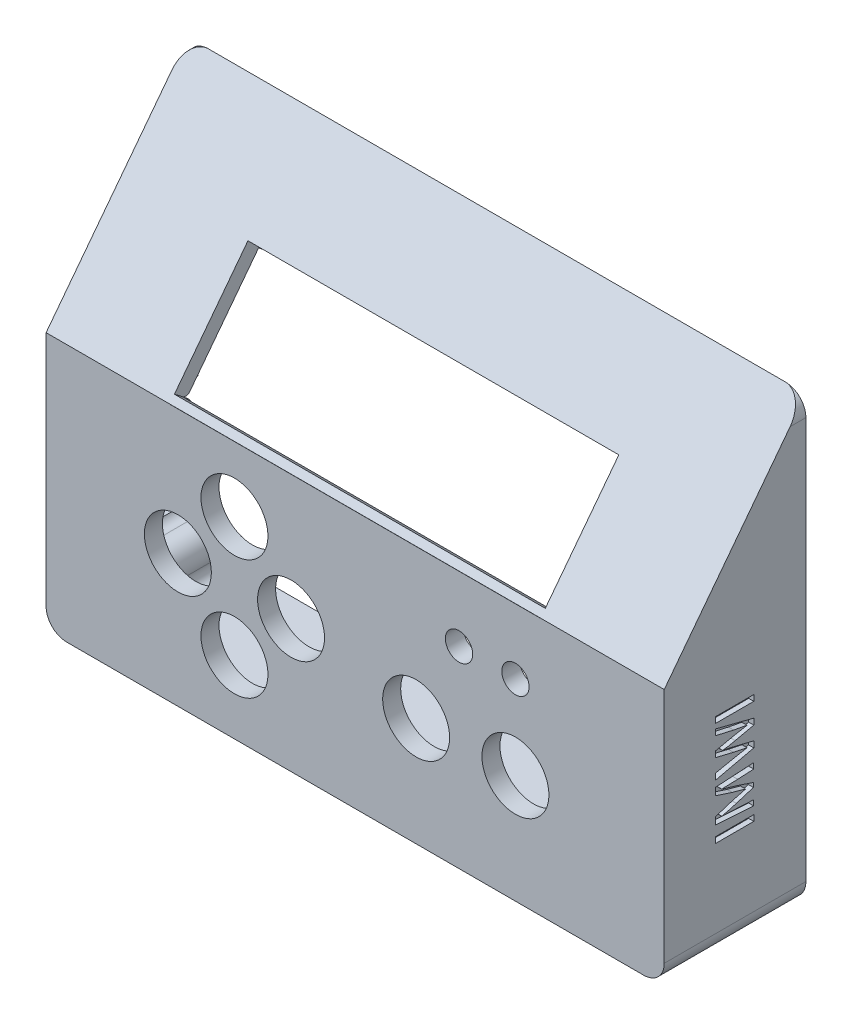
SolidWorks part; units mm, degrees
ref_plane "Front Plane" through (0, 0, 0) normal (0, 0, 1) x (1, 0, 0)
ref_plane "Top Plane" through (0, 0, 0) normal (0, 1, 0) x (1, 0, 0)
ref_plane "Right Plane" through (0, 0, 0) normal (1, 0, 0) x (0, 0, -1)
sketch "Sketch2" plane through (0, 0, 0) normal (0, 0, 1) x (1, 0, 0)
  line L0 (-36, 7) -> (36, 32) construction
  line L1 (-56, -43) -> (56, -43)
  line L2 (-60, -39) -> (-60, 39)
  line L3 (-56, 43) -> (56, 43)
  line L4 (60, -39) -> (60, 39)
  line L5 (-60, -43) -> (60, 43) construction
  line L7 (-36, 32) -> (36, 32)
  line L8 (-36, 32) -> (-36, 7)
  line L9 (-36, 7) -> (36, 7)
  line L10 (36, 32) -> (36, 7)
  line L11 (0, 43) -> (0, -43) construction
  line L12 (-23.4344, -5.6413) -> (-12.4484, -17.2736) construction
  line L13 (-12.4484, -17.2736) -> (-23.4344, -28.9058) construction
  line L14 (-23.4344, -28.9058) -> (-34.4203, -17.2736) construction
  line L15 (-34.4203, -17.2736) -> (-23.4344, -5.6413) construction
  line L16 (-23.4344, -5.6413) -> (-23.4344, -28.9058) construction
  line L17 (-12.4484, -17.2736) -> (-34.4203, -17.2736) construction
  circle A0 centre (-23.4344, -5.6413) radius 6.5
  circle A1 centre (-12.4484, -17.2736) radius 6.5
  circle A2 centre (-34.4203, -17.2736) radius 6.5
  circle A3 centre (-23.4344, -28.9058) radius 6.5
  circle A4 centre (11.8343, -21.8914) radius 6.5
  circle A5 centre (31.1116, -21.8914) radius 6.5
  circle A6 centre (20.1586, -5.6413) radius 2.65
  circle A7 centre (31.1116, -5.6413) radius 2.65
  arc A8 (-56, -43) -> (-60, -39) centre (-56, -39) cw
  arc A9 (56, -43) -> (60, -39) centre (56, -39) ccw
  arc A10 (56, 43) -> (60, 39) centre (56, 39) cw
  arc A11 (-60, 39) -> (-56, 43) centre (-56, 39) cw
  point P0 (0, 0)
  point P20 (0, 19.5)
  point P29 (0, 0)
  point P46 (60, -43)
  dimension "D3" = 72
  dimension "D6" = 11
  dimension "D7" = 4
  dimension "D1" = 86
  dimension "D2" = 120
  dimension "D4" = 25
  dimension "D5" = 16
extrude "Boss-Extrude1" add sketch "Sketch2" along normal blind 2.5
sketch "Sketch3" plane through (0, 0, 0) normal (0, 0, -1) x (-1, 0, 0)
  line L0 (60, 39) -> (60, -39) construction
  line L1 (56, -43) -> (-56, -43) construction
  line L2 (-60, -39) -> (-60, 39) construction
  line L3 (-56, 43) -> (56, 43) construction
  line L4 (60, 39) -> (60, -39)
  line L5 (56, -43) -> (-56, -43)
  line L6 (-60, -39) -> (-60, 39)
  line L7 (-56, 43) -> (56, 43)
  line L9 (-54, 41) -> (54, 41)
  line L10 (-58, 37) -> (-58, -37)
  line L11 (-54, -41) -> (54, -41)
  line L12 (58, 37) -> (58, -37)
  line L13 (-58, 41) -> (58, -41) construction
  line L14 (-58, -41) -> (58, 41) construction
  arc A0 (60, 39) -> (56, 43) centre (56, 39) ccw construction
  arc A1 (56, -43) -> (60, -39) centre (56, -39) ccw construction
  arc A2 (-60, -39) -> (-56, -43) centre (-56, -39) ccw construction
  arc A3 (-56, 43) -> (-60, 39) centre (-56, 39) ccw construction
  arc A4 (60, 39) -> (56, 43) centre (56, 39) ccw
  arc A5 (56, -43) -> (60, -39) centre (56, -39) ccw
  arc A6 (-60, -39) -> (-56, -43) centre (-56, -39) ccw
  arc A7 (-56, 43) -> (-60, 39) centre (-56, 39) ccw
  arc A8 (-58, 37) -> (-54, 41) centre (-54, 37) cw
  arc A9 (-58, -37) -> (-54, -41) centre (-54, -37) ccw
  arc A10 (58, -37) -> (54, -41) centre (54, -37) cw
  arc A11 (54, 41) -> (58, 37) centre (54, 37) cw
  point P3 (0, 0)
  dimension "D5" = 4
  dimension "D1" = 2
  dimension "D2" = 2
  dimension "D3" = 2
  dimension "D4" = 2
extrude "Boss-Extrude2" add sketch "Sketch3" along normal blind 25
sketch "Sketch5" plane through (0, 0, 0) normal (0, 0, -1) x (-1, 0, 0)
  circle A0 centre (23.4344, -28.9058) radius 6.5 construction
  circle A1 centre (34.4203, -17.2736) radius 6.5 construction
  circle A2 centre (23.4344, -5.6413) radius 6.5 construction
  circle A3 centre (12.4484, -17.2736) radius 6.5 construction
  circle A4 centre (-11.8343, -21.8914) radius 6.5 construction
  circle A5 centre (-20.1586, -5.6413) radius 2.65 construction
  circle A6 centre (-31.1116, -5.6413) radius 2.65 construction
  circle A7 centre (-31.1116, -21.8914) radius 6.5 construction
  circle A8 centre (23.4344, -28.9058) radius 6.5
  circle A9 centre (34.4203, -17.2736) radius 6.5
  circle A10 centre (23.4344, -5.6413) radius 6.5
  circle A11 centre (12.4484, -17.2736) radius 6.5
  circle A12 centre (-11.8343, -21.8914) radius 6.5
  circle A13 centre (-20.1586, -5.6413) radius 2.65
  circle A14 centre (-31.1116, -5.6413) radius 2.65
  circle A15 centre (-31.1116, -21.8914) radius 6.5
  circle A16 centre (-31.1116, -5.6413) radius 3.75
  circle A17 centre (-20.1586, -5.6413) radius 3.75
  circle A18 centre (-31.1116, -21.8914) radius 7.5
  circle A19 centre (-11.8343, -21.8914) radius 7.5
  circle A20 centre (12.4484, -17.2736) radius 7.5
  circle A21 centre (23.4344, -5.6413) radius 7.5
  circle A22 centre (34.4203, -17.2736) radius 7.5
  circle A23 centre (23.4344, -28.9058) radius 7.5
sketch "Sketch7" plane through (0, 0, 0) normal (0, 0, -1) x (-1, 0, 0)
  line L0 (0, 41) -> (0, -41) construction
  line L1 (54, 41) -> (-54, 41) construction
  line L2 (-54, -41) -> (54, -41) construction
  line L3 (-58, 0) -> (58, 0) construction
  line L4 (-58, 37) -> (-58, -37) construction
  line L5 (58, -37) -> (58, 37) construction
  line L6 (54, 41) -> (-54, 41) construction
  line L7 (58, -37) -> (58, 37)
  line L8 (54, 41) -> (-54, 41)
  line L9 (-58, -37) -> (-58, 37)
  circle A0 centre (54.5, 37.5) radius 1.7
  arc A1 (53.3, 41) -> (58, 36.3) centre (54.5, 37.5) ccw
  arc A2 (58, 37) -> (54, 41) centre (54, 37) ccw construction
  arc A3 (58, 37) -> (54, 41) centre (54, 37) ccw
  circle A4 centre (54.5, -37.5) radius 1.7
  arc A5 (53.3, -41) -> (58, -36.3) centre (54.5, -37.5) cw
  arc A6 (-53.3, -41) -> (-58, -36.3) centre (-54.5, -37.5) ccw
  circle A7 centre (-54.5, -37.5) radius 1.7
  arc A8 (-58, 37) -> (-54, 41) centre (-54, 37) cw
  arc A9 (-53.3, 41) -> (-58, 36.3) centre (-54.5, 37.5) cw
  circle A10 centre (-54.5, 37.5) radius 1.7
  arc A11 (54, -41) -> (58, -37) centre (54, -37) ccw construction
  arc A12 (-58, -37) -> (-54, -41) centre (-54, -37) ccw construction
  arc A13 (54, -41) -> (58, -37) centre (54, -37) ccw
  arc A14 (-58, -37) -> (-54, -41) centre (-54, -37) ccw
  arc M8 (-54, 41) -> (-58, 37) centre (-54, 37) ccw
  line M9 (-58, 37) -> (-58, -37)
  arc M10 (-58, -37) -> (-54, -41) centre (-54, -37) ccw
  line M11 (-54, -41) -> (54, -41)
  arc M12 (54, -41) -> (58, -37) centre (54, -37) ccw
  line M13 (58, -37) -> (58, 37)
  arc M14 (58, 37) -> (54, 41) centre (54, 37) ccw
  line M15 (54, 41) -> (-54, 41)
  dimension "D1" = 54.5
  dimension "D2" = 37.5
extrude "Boss-Extrude6" add sketch "Sketch7" along normal up to surface (25 mm away) contours A5 A4 M11 M12 M13 | A1 L7 A0 M15 M14 | A9 A10 M15 M8 M9 | A6 L9 A7 M11 M10 region at (-56.7564, -39.7564, 0) region at (-51.9557, 34.9557, 0) region at (53.65, -40.8982, 0) region at (51.9557, 34.9557, 0) up to face at (0, 0, -25)
fillet "Fillet2" radius 2 8 edges at (-53.3, -41, -12.5) (-58, -36.3, -12.5) (53.3, -41, -12.5) (58, -36.3, -12.5) (53.3, 41, -12.5) (58, 36.3, -12.5) (-53.3, 41, -12.5) (-58, 36.3, -12.5)
sketch "Sketch8" plane through (-60, 0, 0) normal (-1, 0, 0) x (0, 0, 1)
  line L0 (-25, -39) -> (-25, 39) construction
  line L1 (-25, -33) -> (-15, -33)
  line L2 (-25, -33) -> (-25, -13)
  line L3 (-25, -13) -> (-15, -13)
  line L4 (-15, -33) -> (-15, -13)
  line L5 (2.5, -43) -> (-25, -43) construction
  dimension "D1" = 20
  dimension "D2" = 10
  dimension "D3" = 10
extrude "Cut-Extrude1" cut sketch "Sketch8" against normal up to next
sketch "Sketch11" plane through (60, 0, 0) normal (1, 0, 0) x (0, 0, -1)
  line L0 (-2.5, 7.0286) -> (25, 43)
  line L1 (-2.5, -39) -> (-2.5, 39) construction
  line L3 (25, 39) -> (25, -39) construction
  line L4 (-2.5, 43) -> (25, 43) construction
  line L5 (25, 43) -> (-2.5, 43)
  line L6 (-2.5, 43) -> (-2.5, 7.0286)
  dimension "D1" = 90
extrude "Cut-Extrude3" cut sketch "Sketch11" against normal blind 127
sketch "Sketch12" plane through (0, 3.7988, 4.9691) normal (0, 0.6073, 0.7944) x (1, 0, 0)
  line L1 (-36, 4.0654) -> (-36, 29.0654)
  line L2 (-36, 29.0654) -> (36, 29.0654)
  line L3 (36, 29.0654) -> (36, 4.0654)
  line L16 (56, 49.3445) -> (-56, 49.3445)
  line L17 (-60, 44.3095) -> (-60, 4.0654)
  line L18 (-60, 4.0654) -> (-36, 4.0654)
  line L19 (-36, 4.0654) -> (-36, 8.1817)
  line L22 (-36, 8.1817) -> (-58, 8.1817)
  line L23 (-58, 8.1817) -> (-58, 35.4994)
  line L24 (-49.0009, 46.827) -> (49.0009, 46.827)
  line L25 (58, 35.4994) -> (58, 8.1817)
  line L26 (58, 8.1817) -> (36, 8.1817)
  line L29 (36, 8.1817) -> (36, 4.0654)
  line L30 (36, 4.0654) -> (60, 4.0654)
  line L31 (60, 4.0654) -> (60, 44.3095)
  line L32 (56, 49.3445) -> (-56, 49.3445)
  line L33 (-60, 44.3095) -> (-60, 4.0654)
  line L34 (-60, 4.0654) -> (-36, 4.0654)
  line L46 (36, 4.0654) -> (60, 4.0654)
  line L47 (60, 4.0654) -> (60, 44.3095)
  ellipse E8 centre (-56, 44.3095) end of major axis (-56, 49.3445) minor radius 4 (-56, 49.3445) -> (-60, 44.3095) ccw
  ellipse E9 centre (-56, 35.4994) end of major axis (-56, 32.9819) minor radius 2 (-55.4737, 37.9281) -> (-58, 35.4994) ccw
  ellipse E10 centre (-54.5, 42.4213) end of major axis (-54.5, 37.764) minor radius 3.7 (-55.4737, 37.9281) -> (-50.9304, 43.647) ccw
  ellipse E11 centre (-49.0009, 44.3095) end of major axis (-49.0009, 41.792) minor radius 2 (-49.0009, 46.827) -> (-50.9304, 43.647) ccw
  ellipse E12 centre (49.0009, 44.3095) end of major axis (49.0009, 41.792) minor radius 2 (50.9304, 43.647) -> (49.0009, 46.827) ccw
  ellipse E13 centre (54.5, 42.4213) end of major axis (54.5, 37.764) minor radius 3.7 (50.9304, 43.647) -> (55.4737, 37.9281) ccw
  ellipse E14 centre (56, 35.4994) end of major axis (56, 32.9819) minor radius 2 (58, 35.4994) -> (55.4737, 37.9281) ccw
  ellipse E15 centre (56, 44.3095) end of major axis (56, 49.3445) minor radius 4 (60, 44.3095) -> (56, 49.3445) ccw
  ellipse E16 centre (-56, 44.3095) end of major axis (-56, 49.3445) minor radius 4 (-56, 49.3445) -> (-60, 44.3095) ccw
  ellipse E23 centre (56, 44.3095) end of major axis (56, 49.3445) minor radius 4 (60, 44.3095) -> (56, 49.3445) ccw
  dimension "D2" = 25
  dimension "D1" = 0
extrude "Boss-Extrude7" add sketch "Sketch12" against normal blind 2
extrude "Boss-Extrude8" add sketch "Sketch5" along normal blind 1
sketch "Sketch14" plane through (-36, 0, 0) normal (1, 0, 0) x (0, 0, -1)
  line L0 (0, 7.0057) -> (-1.5889, 8.2203)
  line L1 (-2.5, 7.0286) -> (12.6836, 26.8895) construction
  line L2 (-1.5889, 8.2203) -> (-2.5, 7.0286)
  line L3 (-2.5, 7.0286) -> (0, 7.0057)
extrude "Boss-Extrude9" add sketch "Sketch14" along normal blind 72
sketch "Sketch15" plane through (0, 2.5842, 3.3802) normal (0, -0.6073, -0.7944) x (-1, 0, 0)
  line L0 (0, 29.0654) -> (0, 5.5656) construction
  line L1 (36, 29.0654) -> (-36, 29.0654) construction
  line L2 (-36, 5.5656) -> (36, 5.5656) construction
  line L3 (-36, 16.6863) -> (36, 16.6863) construction
  line L4 (36, 5.5656) -> (36, 29.0654) construction
  line L5 (-36, 29.0654) -> (-36, 5.5656) construction
  line L6 (-37.875, 29.807) -> (-37.875, 31.807) construction
  line L7 (-38.475, 29.807) -> (-38.475, 31.807)
  line L8 (-37.275, 29.807) -> (-37.275, 31.807)
  line L9 (-39.475, 29.807) -> (-39.475, 31.807)
  line L12 (-37.875, 31.807) -> (-37.875, 29.807) construction
  line L13 (-36.275, 29.807) -> (-36.275, 31.807)
  line L14 (37.875, 29.807) -> (37.875, 31.807) construction
  line L15 (38.475, 29.807) -> (38.475, 31.807)
  line L16 (37.275, 29.807) -> (37.275, 31.807)
  line L17 (36.275, 29.807) -> (36.275, 31.807)
  line L18 (39.475, 29.807) -> (39.475, 31.807)
  line L19 (39.475, 3.5656) -> (39.475, 1.5656)
  line L20 (36.275, 3.5656) -> (36.275, 1.5656)
  line L21 (37.875, 3.5656) -> (37.875, 1.5656) construction
  line L22 (38.475, 3.5656) -> (38.475, 1.5656)
  line L23 (37.275, 3.5656) -> (37.275, 1.5656)
  line L24 (-37.875, 1.5656) -> (-37.875, 3.5656) construction
  line L25 (-36.275, 3.5656) -> (-36.275, 1.5656)
  line L26 (-39.475, 3.5656) -> (-39.475, 1.5656)
  line L27 (-37.875, 3.5656) -> (-37.875, 1.5656) construction
  line L28 (-38.475, 3.5656) -> (-38.475, 1.5656)
  line L29 (-37.275, 3.5656) -> (-37.275, 1.5656)
  arc A0 (-38.475, 29.807) -> (-37.275, 29.807) centre (-37.875, 29.807) ccw
  arc A1 (-37.275, 31.807) -> (-38.475, 31.807) centre (-37.875, 31.807) ccw
  arc A4 (-36.275, 31.807) -> (-39.475, 31.807) centre (-37.875, 31.807) ccw
  arc A5 (-39.475, 29.807) -> (-36.275, 29.807) centre (-37.875, 29.807) ccw
  arc A6 (38.475, 29.807) -> (37.275, 29.807) centre (37.875, 29.807) cw
  arc A7 (37.275, 31.807) -> (38.475, 31.807) centre (37.875, 31.807) cw
  arc A8 (36.275, 31.807) -> (39.475, 31.807) centre (37.875, 31.807) cw
  arc A9 (39.475, 29.807) -> (36.275, 29.807) centre (37.875, 29.807) cw
  arc A10 (39.475, 3.5656) -> (36.275, 3.5656) centre (37.875, 3.5656) ccw
  arc A11 (36.275, 1.5656) -> (39.475, 1.5656) centre (37.875, 1.5656) ccw
  arc A12 (38.475, 3.5656) -> (37.275, 3.5656) centre (37.875, 3.5656) ccw
  arc A13 (37.275, 1.5656) -> (38.475, 1.5656) centre (37.875, 1.5656) ccw
  arc A14 (-39.475, 3.5656) -> (-36.275, 3.5656) centre (-37.875, 3.5656) cw
  arc A15 (-36.275, 1.5656) -> (-39.475, 1.5656) centre (-37.875, 1.5656) cw
  arc A16 (-38.475, 3.5656) -> (-37.275, 3.5656) centre (-37.875, 3.5656) cw
  arc A17 (-37.275, 1.5656) -> (-38.475, 1.5656) centre (-37.875, 1.5656) cw
  point P11 (-37.875, 30.807)
  point P20 (-37.875, 30.807)
  point P26 (-37.6484, 30.807)
  point P31 (37.875, 30.807)
  point P48 (37.875, 2.5656)
  point P56 (-37.875, 2.5656)
  point P60 (-37.875, 2.5656)
  dimension "D1" = 0.6
  dimension "D2" = 1
  dimension "D3" = 2
  dimension "D4" = 75.75
  dimension "D5" = 3
sketch "Sketch16" plane through (0, 2.5842, 3.3802) normal (0, -0.6073, -0.7944) x (-1, 0, 0)
  line L0 (36, 5.5656) -> (36, 29.0654) construction
  line L2 (-36, 29.0654) -> (-36, 5.5656) construction
  line L3 (36, 29.0654) -> (-36, 29.0654) construction
  line L4 (36, 5.5656) -> (36, 29.0654)
  line L6 (-36, 29.0654) -> (-36, 5.5656)
  line L7 (36, 29.0654) -> (-36, 29.0654)
  line L8 (37, 30.0654) -> (-37, 30.0654)
  line L9 (-37, 30.0654) -> (-37, 5.5656)
  line L11 (37, 5.5656) -> (37, 30.0654)
  line L12 (-36, 5.5656) -> (-37, 5.5656)
  line L13 (-36, 5.5656) -> (-58, 5.5656) construction
  line L14 (-37, 30.0654) -> (-37, 4.5656) construction
  line L15 (-37, 4.5656) -> (37, 4.5656) construction
  line L16 (-36, 5.5656) -> (36, 5.5656) construction
  line L17 (36, 5.5656) -> (37, 5.5656)
  line L18 (58, 5.5656) -> (36, 5.5656) construction
  line L19 (37, 4.5656) -> (37, 30.0654) construction
  dimension "D1" = 1
extrude "Boss-Extrude11" add sketch "Sketch16" along normal blind 1
sketch "Sketch17" plane through (60, 0, 0) normal (1, 0, 0) x (0, 0, -1)
  line L0 (14.8983, -24.5685) -> (14.8983, 0.4315) construction
  text T0 "IMWI\r\n" font "@Adobe Heiti Std R" height in points 24
  point P3 (15.0306, -7.3724)
  point P4 (17.8318, -32.4816)
  point P5 (15.445, -27.7686)
  point P6 (17.2582, -14.9359)
  point P7 (14.2683, -27.4953)
  point P8 (15.0056, -26.0122)
  point P9 (14.4061, -27.6842)
  point P10 (14.8983, -24.5685)
  dimension "D1" = 25
extrude "Cut-Extrude4" cut sketch "Sketch17" against normal blind 1
extrude "Boss-Extrude12" add sketch "Sketch15" along normal blind 4
sketch "Sketch19" plane through (60, 0, 0) normal (1, 0, 0) x (0, 0, -1)
  line L0 (-2.5, 7.0286) -> (-2.5, 1.4089)
  line L1 (-2.5, -39) -> (-2.5, 7.0286) construction
  line L2 (-2.5, 1.4089) -> (-11.7676, 1.4089)
  line L3 (-11.7676, 1.4089) -> (-11.7676, 7.0286)
  line L4 (-11.7676, 7.0286) -> (-2.5, 7.0286)
extrude "Cut-Extrude5" cut sketch "Sketch19" against normal blind 123
sketch "Sketch20" plane through (0, 0.1548, 0.2025) normal (0, -0.6073, -0.7944) x (-1, 0, 0)
  line L0 (-38.475, 3.5656) -> (-38.475, 1.5656) construction
  line L1 (-37.275, 1.5656) -> (-37.275, 3.5656) construction
  line L2 (-38.475, 3.5656) -> (-38.475, 1.5656)
  line L3 (-37.275, 1.5656) -> (-37.275, 3.5656)
  line L4 (38.475, 1.5656) -> (38.475, 3.5656) construction
  line L5 (38.475, 1.5656) -> (38.475, 3.5656)
  line L9 (37.275, 3.5656) -> (37.275, 1.5656) construction
  line L10 (37.275, 3.5656) -> (37.275, 1.5656)
  arc A0 (-38.475, 1.5656) -> (-37.275, 1.5656) centre (-37.875, 1.5656) ccw construction
  arc A1 (-37.275, 3.5656) -> (-38.475, 3.5656) centre (-37.875, 3.5656) ccw construction
  arc A2 (-38.475, 1.5656) -> (-37.275, 1.5656) centre (-37.875, 1.5656) ccw
  arc A3 (-37.275, 3.5656) -> (-38.475, 3.5656) centre (-37.875, 3.5656) ccw
  arc A4 (37.275, 1.5656) -> (38.475, 1.5656) centre (37.875, 1.5656) ccw construction
  arc A5 (37.275, 1.5656) -> (38.475, 1.5656) centre (37.875, 1.5656) ccw
  arc A9 (38.475, 3.5656) -> (37.275, 3.5656) centre (37.875, 3.5656) ccw construction
  arc A10 (38.475, 3.5656) -> (37.275, 3.5656) centre (37.875, 3.5656) ccw
extrude "Cut-Extrude6" cut sketch "Sketch20" against normal blind 3
sketch "Sketch21" plane through (-60, 0, 0) normal (-1, 0, 0) x (0, 0, 1)
  line L0 (-25, 39) -> (-25, 47.9365)
  line L1 (-25, 47.9365) -> (-33.4303, 47.9365)
  line L2 (-33.4303, 47.9365) -> (-33.4303, 39)
  line L3 (-33.4303, 39) -> (-25, 39)
extrude "Cut-Extrude7" cut sketch "Sketch21" against normal blind 163
fillet "Fillet3" radius 1 11 edges at (36.275, 27.1611, -15.4087) (38.6366, 25.1461, -13.8683) (39.475, 27.0584, -15.3302) (-38.6366, 25.1461, -13.8683) (-39.475, 27.0584, -15.3302) (-36.275, 27.1611, -15.4087) (36.5, 6.3983, -0.7944) (-36.5, 6.3983, -0.7944) (37.875, 0.4196, 0) (37.875, 29.124, -16.9093) (-37.875, 29.124, -16.9093)
sketch "Sketch22" plane through (0, 0, -25) normal (0, 0, -1) x (-1, 0, 0)
  circle A0 centre (-54.5, 37.5) radius 1.7 construction
  circle A1 centre (54.5, 37.5) radius 1.7 construction
  circle A2 centre (-54.5, 37.5) radius 1.7
  circle A3 centre (54.5, 37.5) radius 1.7
  circle A4 centre (54.5, 37.5) radius 0.6
  circle A5 centre (-54.5, 37.5) radius 0.6
  dimension "D1" = 1.2
extrude "Boss-Extrude13" add sketch "Sketch22" against normal blind 5
sketch "Sketch23" plane through (60, 0, 0) normal (1, 0, 0) x (0, 0, -1)
  line L0 (19.0782, 35.254) -> (23.1805, 40.62)
  line L1 (-2.5, 7.0286) -> (21.942, 39) construction
  line L2 (23.1805, 40.62) -> (17.8165, 44.7207)
  line L3 (17.8165, 44.7207) -> (13.7142, 39.3547)
  line L4 (13.7142, 39.3547) -> (19.0782, 35.254)
extrude "Cut-Extrude8" cut sketch "Sketch23" against normal blind 131
